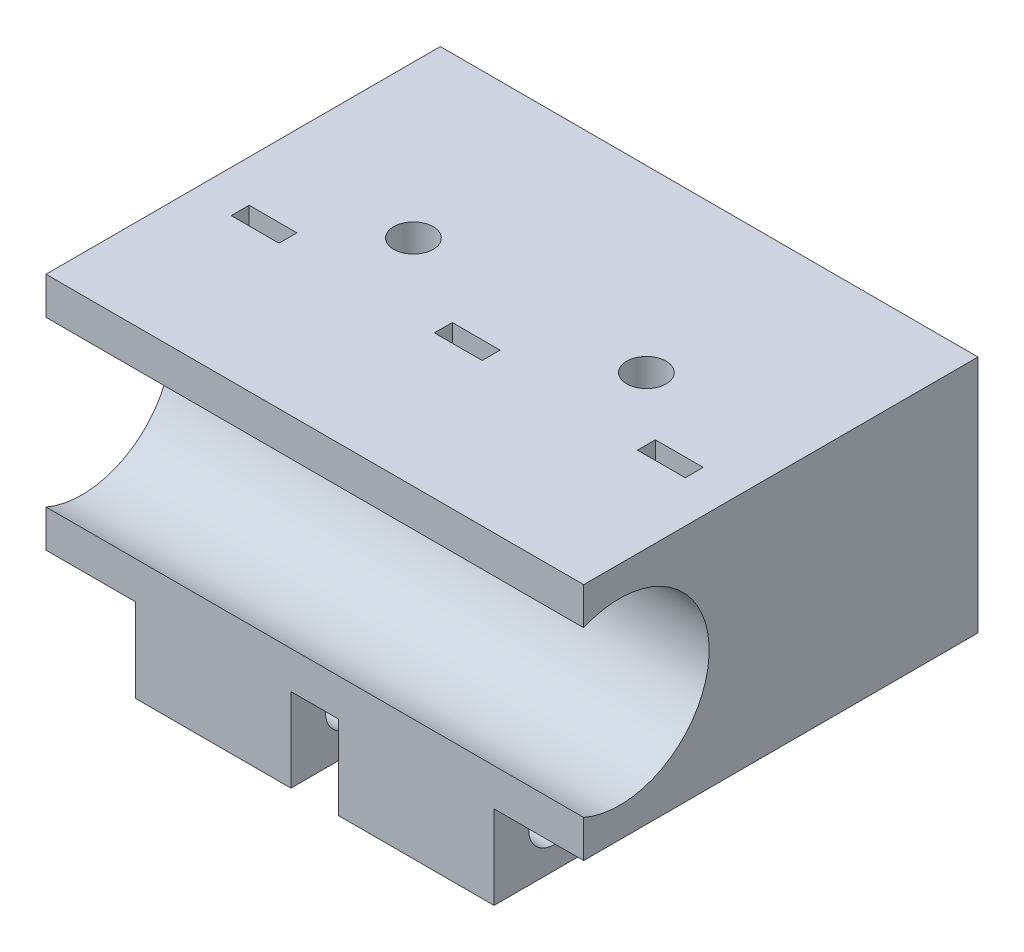
SolidWorks part; units mm, degrees
ref_plane "Front Plane" through (0, 0, 0) normal (0, 0, 1) x (1, 0, 0)
ref_plane "Top Plane" through (0, 0, 0) normal (0, 1, 0) x (1, 0, 0)
ref_plane "Right Plane" through (0, 0, 0) normal (1, 0, 0) x (0, 0, -1)
sketch "Sketch2" plane through (0, 0, 0) normal (0, 0, 1) x (1, 0, 0)
  line L1 (22.5, 10) -> (-22.5, 10)
  line L2 (22.5, 10) -> (22.5, -10)
  line L3 (22.5, -10) -> (-22.5, -10)
  line L4 (-22.5, 10) -> (-22.5, -10)
  line L5 (22.5, 10) -> (-22.5, -10) construction
  line L6 (22.5, -10) -> (-22.5, 10) construction
  point P0 (0, 0)
  dimension "D1" = 20
  dimension "D2" = 45
extrude "Boss-Extrude1" add sketch "Sketch2" along normal blind 33
sketch "Sketch3" plane through (22.5, 0, 0) normal (1, 0, 0) x (0, 0, -1)
  line L0 (-30, 0) -> (0, 0) construction
  circle A0 centre (-30, 0) radius 7.5
  dimension "D1" = 15
  dimension "D2" = 30
extrude "Cut-Extrude1" cut sketch "Sketch3" against normal blind 45
sketch "Sketch4" plane through (0, 0, 0) normal (0, 0, -1) x (-1, 0, 0)
  line L4 (22.5, -10) -> (22.5, 10)
  line L5 (22.5, 10) -> (-22.5, 10)
  line L6 (-22.5, 10) -> (-22.5, -10)
  line L7 (-22.5, -10) -> (22.5, -10)
  line L8 (22.5, -10) -> (22.5, 10)
  line L9 (22.5, 10) -> (-22.5, 10)
  line L10 (-22.5, 10) -> (-22.5, -10)
  line L11 (-22.5, -10) -> (22.5, -10)
  circle A0 centre (-15, 0) radius 4
  circle A1 centre (15, 0) radius 4
  dimension "D2" = 8
  dimension "D3" = 30
  dimension "D4" = 15
  dimension "D1" = 0
extrude "Cut-Extrude2" cut sketch "Sketch4" against normal blind 10 contours A0 | A1 region at (15, 0, 0) region at (-15, 0, 0)
sketch "Sketch5" plane through (0, -10, 0) normal (0, -1, 0) x (1, 0, 0)
  line L0 (0, 19.5) -> (0, 0) construction
  line L1 (-19, 21) -> (-15, 21)
  line L2 (-19, 21) -> (-19, 19.5)
  line L3 (-19, 19.5) -> (-15, 19.5)
  line L4 (-15, 21) -> (-15, 19.5)
  line L5 (-2, 19.5) -> (2, 19.5)
  line L6 (-2, 19.5) -> (-2, 21)
  line L7 (-2, 21) -> (2, 21)
  line L8 (2, 19.5) -> (2, 21)
  line L9 (15, 19.5) -> (19, 19.5)
  line L10 (15, 19.5) -> (15, 21)
  line L11 (15, 21) -> (19, 21)
  line L12 (19, 19.5) -> (19, 21)
  line L13 (-22.5, 19.5) -> (-19, 19.5) construction
  line L14 (-22.5, 33) -> (-22.5, 0) construction
  line L15 (-2, 19.5) -> (-15, 19.5) construction
  line L16 (2, 19.5) -> (15, 19.5) construction
  line L17 (19, 19.5) -> (22.5, 19.5) construction
  line L18 (22.5, 33) -> (22.5, 0) construction
  line L27 (-22.5, 0) -> (22.5, 0) construction
  dimension "D1" = 4
  dimension "D2" = 1.5
  dimension "D3" = 30
  dimension "D4" = 21
extrude "Cut-Extrude3" cut sketch "Sketch5" against normal blind 39
fillet "Fillet1" radius 9 3 edges at (17, -10, 21) (0, -10, 21) (-17, -10, 21)
hole_wizard "M4x0.7 Tapped Hole1" positions "Sketch7" profile "Sketch6" tap size "M4x0.7" standard "ANSI Metric" end condition through all
sketch "Sketch7" plane through (0, -10, 0) normal (0, -1, 0) x (-1, 0, 0)
  line L0 (0, 0) -> (0, -15) construction
  line L3 (9.75, -15) -> (-9.75, -15) construction
  point P0 (-9.75, -15)
  point P2 (9.75, -15)
  dimension "D1" = 19.5
  dimension "D2" = 15
cosmetic thread "Hole Thread1" parameters "D2"=4
cosmetic thread "Hole Thread2" parameters "D2"=4
sketch "Sketch6" plane through (9.75, -10, 15) normal (1, 0, 0) x (0, 0, -1)
  line L0 (0, 0) -> (0, 20)
  line L1 (0, 20) -> (1.65, 20)
  line L2 (1.65, 20) -> (1.65, 0)
  line L5 (1.65, 0) -> (0, 0)
  line L11 (0, -6.35) -> (0, 107.95) construction
  dimension "Thru Tap Drill Dia." = 3.3
  dimension "Thru Tap Drill Depth" = 20
sketch "Sketch8" plane through (0, -10, 0) normal (0, -1, 0) x (1, 0, 0)
  line L0 (-22.5, 33) -> (22.5, 33) construction
  line L1 (-15, 23) -> (-2, 23)
  line L2 (-15, 23) -> (-15, 33)
  line L3 (-15, 33) -> (-2, 33)
  line L4 (-2, 23) -> (-2, 33)
  line L5 (2, 23) -> (15, 23)
  line L6 (2, 23) -> (2, 33)
  line L7 (2, 33) -> (15, 33)
  line L8 (15, 23) -> (15, 33)
  line L9 (-15, 30) -> (-15, 21) construction
  line L13 (15, 21) -> (15, 30) construction
  line L14 (-2, 21) -> (-2, 30) construction
  dimension "D2" = 10
extrude "Boss-Extrude2" add sketch "Sketch8" along normal blind 7
sketch "Sketch14" plane through (-15, 0, 0) normal (-1, 0, 0) x (0, 0, 1)
  line L0 (33, -10) -> (0, -10) construction
  line L1 (28, -13) -> (28, -17) construction
  line L2 (33, -17) -> (23, -17) construction
  circle A0 centre (28, -13) radius 2.1
  dimension "D1" = 4.2
  dimension "D2" = 3
extrude "Cut-Extrude6" cut sketch "Sketch14" against normal through all
